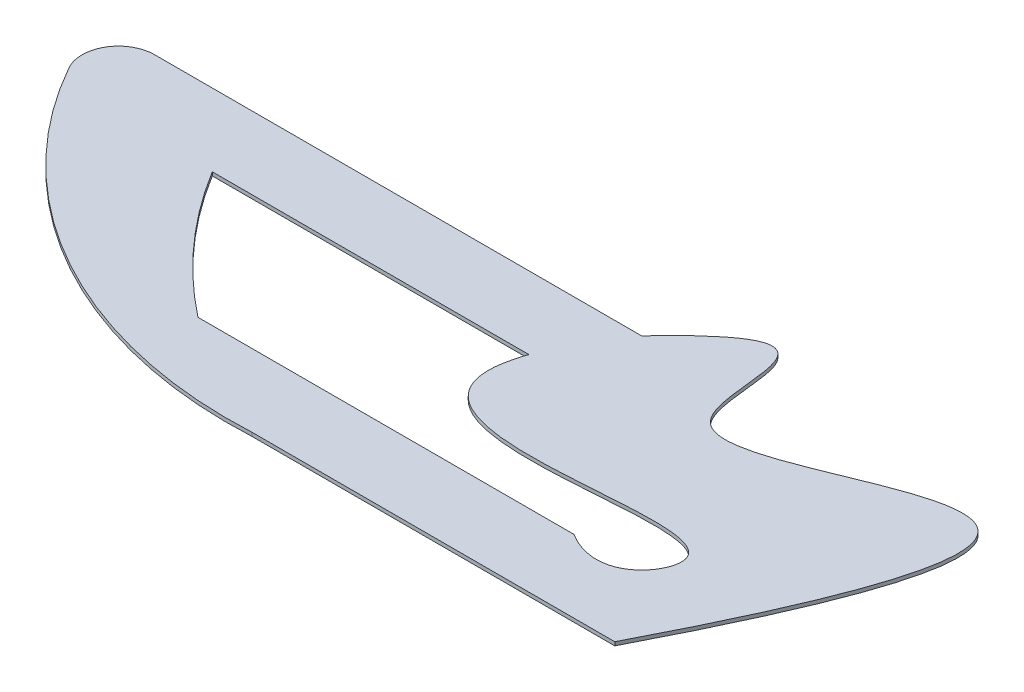
SolidWorks part; units mm, degrees
ref_plane "Front Plane" through (0, 0, 0) normal (0, 0, 1) x (1, 0, 0)
ref_plane "Top Plane" through (0, 0, 0) normal (0, 1, 0) x (1, 0, 0)
ref_plane "Right Plane" through (0, 0, 0) normal (1, 0, 0) x (0, 0, -1)
sketch "Sketch1" plane through (0, 0, 0) normal (0, 1, 0) x (1, 0, 0)
  line L0 (30997.3173, 12512.9227) -> (82807.7997, 12512.9227)
  line L1 (48437.5944, 2512.9227) -> (98437.5944, 2512.9227)
  line L2 (-3324.611, 40868.6424) -> (63779.7765, 40868.6424)
  line L3 (14612.8057, 30868.6424) -> (58250.5658, 30868.6424)
  arc A0 (-7685.4254, 33422.5644) -> (48437.5944, 2512.9227) centre (45236.9332, 63107.8949) ccw
  arc A1 (30997.3173, 12512.9227) -> (14612.8057, 30868.6424) centre (73630.5941, 67058.196) cw
  arc A2 (-3324.611, 40868.6424) -> (-7685.4254, 33422.5644) centre (-3324.611, 35868.6424) ccw
  spline S0 degree 3 poles (58250.5658, 30868.6424) (50714.5989, 9071.3526) (106640.4429, 30970.0527) (89500.8389, 8357.3962) (82807.7997, 12512.9227) knots 0 0 0 0 0.742821 1 1 1 1
  spline S1 degree 3 poles (63779.7765, 40868.6424) (81155.1096, 59417.4788) (61765.4618, 3316.6124) (133877.925, 71175.9339) (98437.5944, 2512.9227) knots 0 0 0 0 0.353581 1 1 1 1
  point P23 (-11220.2235, 40868.6424)
  dimension "D3" = 10000
  dimension "D4" = 5000
  dimension "D5" = 10000
  dimension "D2" = 50000
  dimension "D1" = 75000
extrude "Boss-Extrude1" add sketch "Sketch1" along normal blind 500
